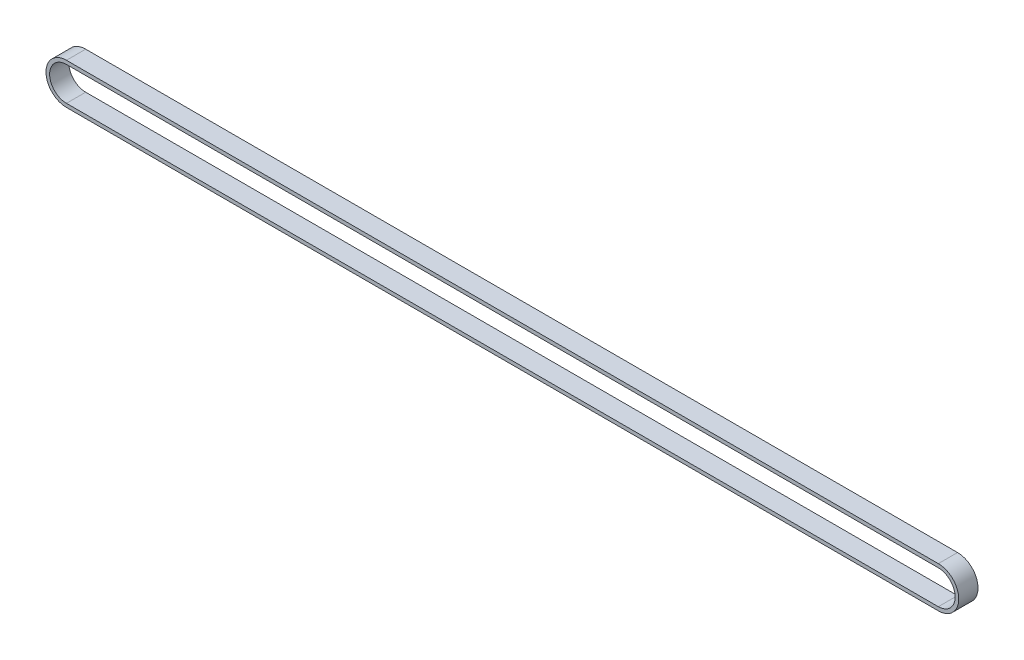
SolidWorks part; units mm, degrees
material "PF"
ref_plane "Piano frontale" through (0, 0, 0) normal (0, 0, 1) x (1, 0, 0)
ref_plane "Piano superiore" through (0, 0, 0) normal (0, 1, 0) x (1, 0, 0)
ref_plane "Piano destro" through (0, 0, 0) normal (1, 0, 0) x (0, 0, -1)
sketch "Schizzo1" plane through (0, 0, 0) normal (0, 0, 1) x (1, 0, 0)
  line L0 (0, 0) -> (-290, 0) construction
  line L1 (0, -5.6) -> (-290, -5.6)
  line L2 (0, 5.6) -> (-290, 5.6)
  line L3 (0, 0) -> (-290, 0) construction
  line L4 (0, -6.8) -> (-290, -6.8)
  line L5 (0, 6.8) -> (-290, 6.8)
  arc A0 (0, -5.6) -> (0, 5.6) centre (0, 0) ccw
  arc A1 (-290, 5.6) -> (-290, -5.6) centre (-290, 0) ccw
  arc A2 (0, -6.8) -> (0, 6.8) centre (0, 0) ccw
  arc A3 (-290, 6.8) -> (-290, -6.8) centre (-290, 0) ccw
  point P3 (-145, 0)
  point P8 (-145, 0)
  dimension "D3" = 5.6
  dimension "D1" = 1.2
  dimension "D2" = 290
extrude "Estrusione-Estrusione1" add sketch "Schizzo1" along normal blind 6.4
